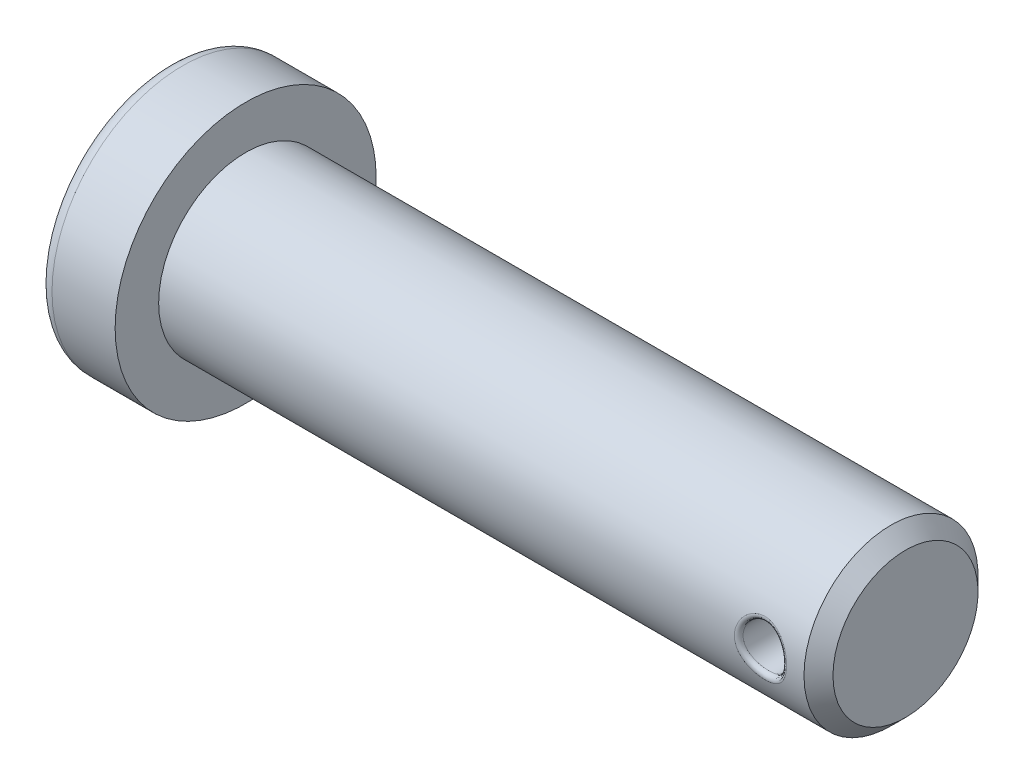
SolidWorks part; units mm, degrees
ref_plane "Face" through (0, 0, 0) normal (0, 0, 1) x (1, 0, 0)
ref_plane "Dessus" through (0, 0, 0) normal (0, 1, 0) x (1, 0, 0)
ref_plane "Droite" through (0, 0, 0) normal (1, 0, 0) x (0, 0, -1)
sketch "Esquisse1" plane through (0, 0, 0) normal (0, 0, 1) x (1, 0, 0)
  line L0 (-48.6322, 0) -> (70.2693, 0) construction
  line L1 (34.3232, 0) -> (34.3232, 5)
  line L2 (34.3232, 5) -> (33.3232, 6)
  line L3 (33.3232, 6) -> (-11.1768, 6)
  line L4 (-11.1768, 6) -> (-11.1768, 9)
  line L5 (-11.1768, 9) -> (-16.1768, 9)
  line L6 (-16.1768, 9) -> (-16.1768, 0)
  line L7 (34.3232, 0) -> (-16.1768, 0)
  dimension "D1" = 6
  dimension "D2" = 1
  dimension "D3" = 1
  dimension "D4" = 45.5
  dimension "D5" = 5
  dimension "D6" = 9
revolve "Révolution1" add sketch "Esquisse1" angle 360 about L0
sketch "Esquisse2" plane through (0, 0, 0) normal (0, 0, 1) x (1, 0, 0)
  line L0 (34.3232, -5) -> (34.3232, 5) construction
  circle A0 centre (30.3232, 0) radius 1.5
  dimension "D1" = 3
  dimension "D2" = 4
extrude "Enlèv. mat.-Extru.1" cut sketch "Esquisse2" against normal through all and the other way through all
fillet "Congé1" radius 0.3 2 edges at (28.8522, 0.2934, 5.9928) (28.8522, -0.2934, -5.9928)
dome "Dôme1" faces to dome 1 distance 2 reverse direction no elliptical dome no face at (-16.1768, 0, 9) parameters "D1"=2
fillet "Congé2" radius 1 1 edges at (-16.1768, 0, 9)
